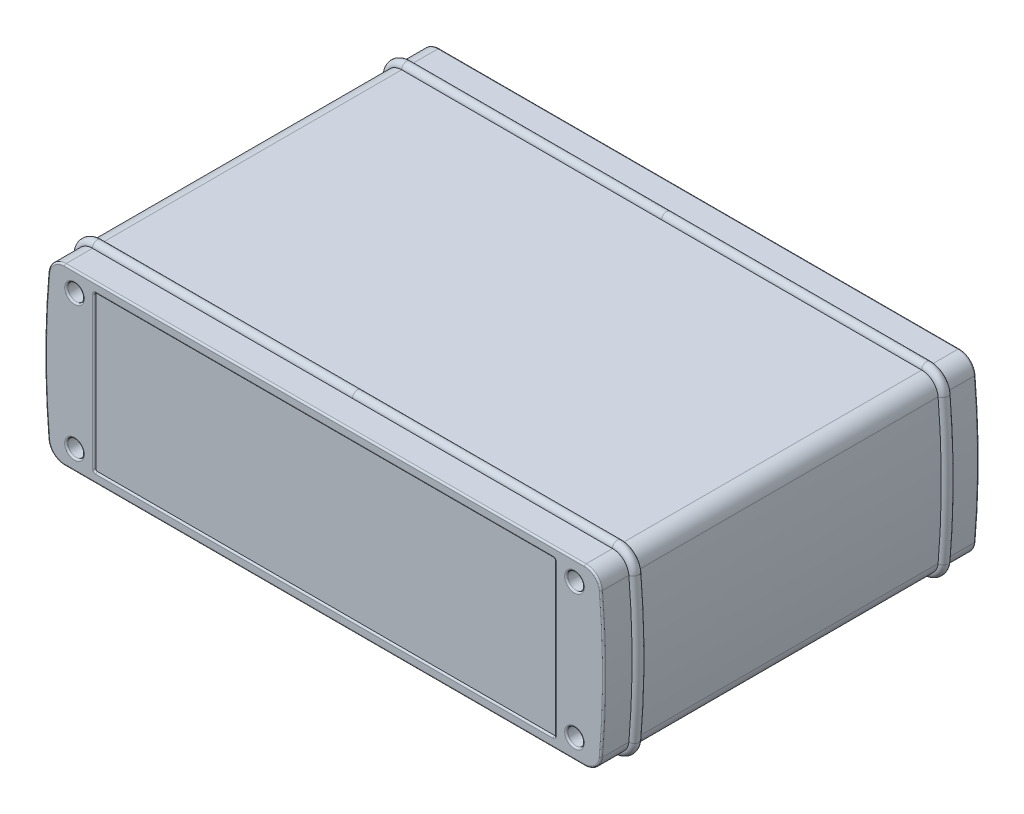
SolidWorks part; units mm, degrees
material "ABS"
ref_plane "Front Plane" through (0, 0, 0) normal (0, 0, 1) x (1, 0, 0)
ref_plane "Top Plane" through (0, 0, 0) normal (0, 1, 0) x (1, 0, 0)
ref_plane "Right Plane" through (0, 0, 0) normal (1, 0, 0) x (0, 0, -1)
sketch "Sketch1" plane through (0, 0, 0) normal (0, 0, 1) x (1, 0, 0)
  line L1 (0, 0) -> (172, 0)
  line L2 (0, 0) -> (0, 53)
  line L3 (0, 53) -> (172, 53)
  line L4 (172, 0) -> (172, 53)
  dimension "D1" = 53
  dimension "D2" = 172
extrude "Boss-Extrude1" add sketch "Sketch1" along normal blind 114
sketch "Sketch2" plane through (0, 0, 114) normal (0, 0, 1) x (1, 0, 0)
  line L0 (0, 26.5) -> (172, 26.5) construction
  line L1 (0, 53) -> (0, 0) construction
  line L2 (172, 0) -> (172, 53) construction
  line L4 (-106.1336, 125.318) -> (21.359, 125.318)
  line L5 (-106.1336, 125.318) -> (-106.1336, -46.2039)
  line L6 (-106.1336, -46.2039) -> (11.8052, -46.2039)
  arc A0 (21.359, 125.318) -> (11.8052, -46.2039) centre (251, 26.5) ccw
  dimension "D1" = 500
  dimension "D2" = 251
extrude "Cut-Extrude1" cut sketch "Sketch2" against normal through all
ref_plane "Plane1" through (86, 0, 0) normal (1, 0, 0) x (0, 0, -1)
mirror "Mirror1" about plane through (86, 0, 0) normal (1, 0, 0) of "Cut-Extrude1"
fillet "Fillet1" radius 5 4 edges at (2.4085, 0, 57) (169.5915, 0, 57) (169.5915, 53, 57) (2.4085, 53, 57)
ref_plane "Plane2" through (0, 0, 104) normal (0, 0, 1) x (1, 0, 0)
sketch "Sketch3" plane through (0, 0, 104) normal (0, 0, 1) x (1, 0, 0)
  line L2 (6.9452, 0) -> (165.0548, 0)
  line L3 (165.0548, 53) -> (6.9452, 53)
  line L4 (6.9452, 0) -> (165.0548, 0)
  line L5 (165.0548, 53) -> (6.9452, 53)
  arc A6 (1.9645, 48.4388) -> (1.9645, 4.5612) centre (251, 26.5) ccw
  arc A7 (1.9645, 4.5612) -> (6.9452, 0) centre (6.9452, 5) ccw
  arc A8 (165.0548, 0) -> (170.0355, 4.5612) centre (165.0548, 5) ccw
  arc A9 (170.0355, 4.5612) -> (170.0355, 48.4388) centre (-79, 26.5) ccw
  arc A10 (170.0355, 48.4388) -> (165.0548, 53) centre (165.0548, 48) ccw
  arc A11 (6.9452, 53) -> (1.9645, 48.4388) centre (6.9452, 48) ccw
  arc A12 (1.9645, 48.4388) -> (1.9645, 4.5612) centre (251, 26.5) ccw
  arc A13 (1.9645, 4.5612) -> (6.9452, 0) centre (6.9452, 5) ccw
  arc A14 (165.0548, 0) -> (170.0355, 4.5612) centre (165.0548, 5) ccw
  arc A15 (170.0355, 4.5612) -> (170.0355, 48.4388) centre (-79, 26.5) ccw
  arc A16 (170.0355, 48.4388) -> (165.0548, 53) centre (165.0548, 48) ccw
  arc A17 (6.9452, 53) -> (1.9645, 48.4388) centre (6.9452, 48) ccw
  dimension "D1" = 0
sketch "Sketch4" plane through (86, 0, 0) normal (1, 0, 0) x (0, 0, -1)
  line L0 (-104, 53) -> (-104, 48.4388) construction
  line L1 (0, 53) -> (-114, 53) construction
  line L2 (-102.5, 53) -> (-105.5, 53)
  arc A0 (-102.5, 53) -> (-105.5, 53) centre (-104, 53) ccw
  dimension "D1" = 3
sweep "Sweep1" add profiles "Sketch4" path "Sketch3"
ref_plane "Plane3" through (0, 0, 57) normal (0, 0, 1) x (1, 0, 0)
mirror "Mirror2" about plane through (0, 0, 57) normal (0, 0, 1) of "Sweep1"
sketch "Sketch5" plane through (0, 0, 114) normal (0, 0, 1) x (1, 0, 0)
  line L0 (165.0548, 53) -> (6.9452, 53) construction
  line L1 (16, 50) -> (156, 50)
  line L2 (16, 50) -> (16, 3)
  line L3 (16, 3) -> (156, 3)
  line L4 (156, 50) -> (156, 3)
  line L5 (6.9452, 0) -> (165.0548, 0) construction
  arc A0 (171.5297, 4.4296) -> (171.5297, 48.5704) centre (-79, 26.5) ccw construction
  arc A1 (0.4703, 48.5704) -> (0.4703, 4.4296) centre (251, 26.5) ccw construction
  dimension "D1" = 3
  dimension "D2" = 3
  dimension "D3" = 235
  dimension "D4" = 235
extrude "Cut-Extrude2" cut sketch "Sketch5" against normal blind 0.5 contours L2 L3 L4 L1
fillet "Fillet2" radius 0.5 4 edges at (86, 3, 114) (156, 26.5, 114) (16, 26.5, 114) (86, 50, 114)
fillet "Fillet3" radius 0.5 16 edges at (168.4317, 51.6874, 0) (171, 26.5, 0) (168.4317, 1.3126, 0) (86, 0, 0) (3.5683, 1.3126, 0) (1, 26.5, 0) (3.5683, 51.6874, 0) (168.4317, 1.3126, 114) (86, 0, 114) (3.5683, 1.3126, 114) (1, 26.5, 114) (3.5683, 51.6874, 114) (86, 53, 114) (168.4317, 51.6874, 114) (86, 53, 0) (171, 26.5, 114)
sketch "Sketch6" plane through (0, 0, 114) normal (0, 0, 1) x (1, 0, 0)
  circle A0 centre (10, 47) radius 2.5
  dimension "D1" = 5
  dimension "D2" = 10
  dimension "D3" = 47
extrude "Cut-Extrude3" cut sketch "Sketch6" against normal blind 5
mirror "Mirror3" about plane through (86, 0, 0) normal (1, 0, 0) of "Cut-Extrude3"
ref_plane "Plane4" through (0, 26.5, 0) normal (0, 1, 0) x (1, 0, 0)
mirror "Mirror4" about plane through (0, 26.5, 0) normal (0, 1, 0) of "Mirror3", "Cut-Extrude3"
fillet "Fillet4" radius 0.5 4 edges at (159.5, 47, 114) (159.5, 6, 114) (12.5, 6, 114) (12.5, 47, 114)
